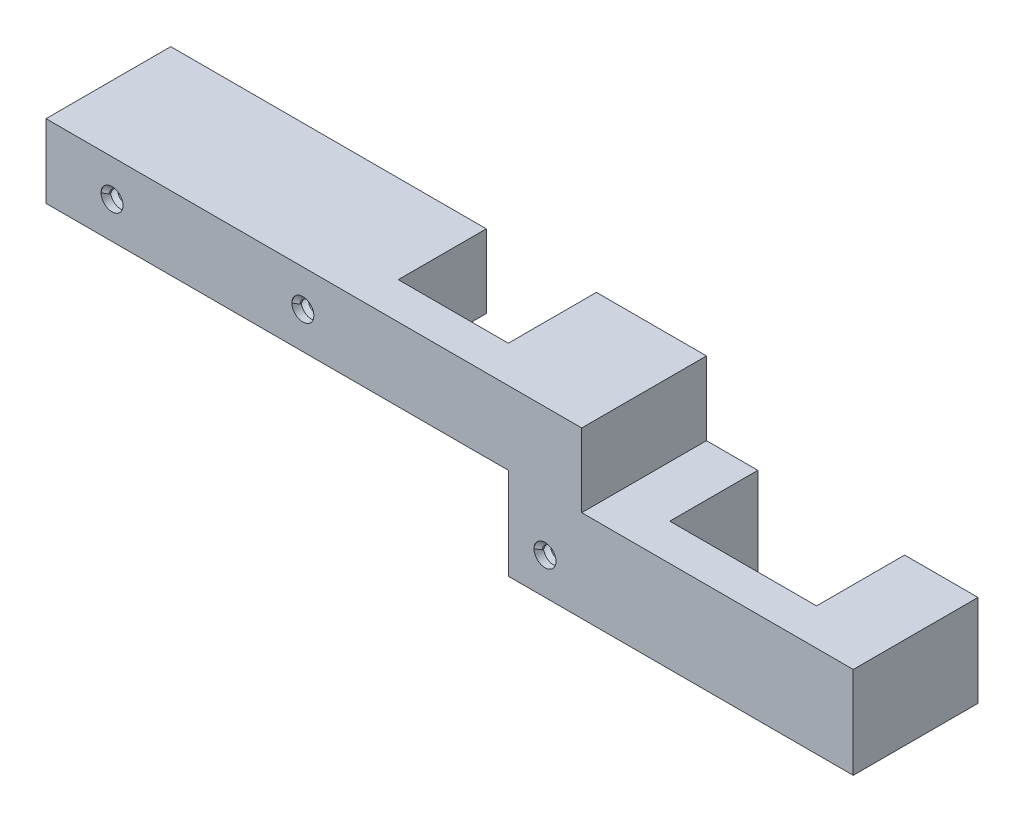
SolidWorks part; units mm, degrees
ref_plane "Alzado" through (0, 0, 0) normal (0, 0, 1) x (1, 0, 0)
ref_plane "Planta" through (0, 0, 0) normal (0, 1, 0) x (1, 0, 0)
ref_plane "Vista lateral" through (0, 0, 0) normal (1, 0, 0) x (0, 0, -1)
sketch "Croquis1" plane through (0, 0, 0) normal (0, 0, 1) x (1, 0, 0)
  line L0 (-66.626, 7.7371) -> (-3.626, 7.7371)
  line L2 (-66.626, 17.7371) -> (-66.626, 7.7371)
  line L6 (-3.626, 7.7371) -> (-3.626, -4.7629)
  line L7 (-3.626, -4.7629) -> (43.374, -4.7629)
  line L8 (43.374, 7.7371) -> (43.374, -4.7629)
  line L9 (6.374, 7.7371) -> (43.374, 7.7371)
  line L10 (6.374, 7.7371) -> (6.374, 17.7371)
  line L11 (6.374, 17.7371) -> (-66.626, 17.7371)
  circle A0 centre (-31.626, 12.7371) radius 1.5
  circle A1 centre (-57.626, 12.7371) radius 1.5
  circle A2 centre (1.374, 0.2371) radius 1.5
  dimension "D4" = 3
  dimension "D5" = 3
  dimension "D7" = 3
  dimension "D2" = 10
  dimension "D6" = 26
  dimension "D11" = 5
  dimension "D12" = 5
extrude "Saliente-Extruir1" add sketch "Croquis1" along normal blind 17
thread "Rosca1" pitch 1.25 method extrude profile "Perfil de rosca1" start angle 0, offset 0, length 15, pitch 1.25, diameter 3
ref_plane "Plano1" through (-33.126, 12.7371, 17) normal (0, -1, 0) x (-1, 0, 0)
sketch "Perfil de rosca1" plane through (-33.126, 12.7371, 17) normal (0, -1, 0) x (-1, 0, 0)
  line L0 (0, 0) -> (0, 1.25) construction
  line L11 (0, 0) -> (0, 1.0937)
  line L12 (0, 1.0937) -> (-0.6766, 0.7031)
  line L13 (-0.6766, 0.7031) -> (-0.6766, 0.3906)
  line L15 (-0.6766, 0.3906) -> (0, 0)
  line L17 (-0.6766, 0.5469) -> (0, 0.5469) construction
  point P2 (0, 0)
  dimension "Pitch" = 1.25
  dimension "Profile_Angle" = 60
  dimension "Profile_Land" = 0.3125
  dimension "Profile_Height" = 0.6766
thread "Rosca2" pitch 1.25 method extrude profile "Perfil de rosca2" start angle 0, offset 0, length 15, pitch 1.25, diameter 3
ref_plane "Plano2" through (-59.126, 12.7371, 17) normal (0, -1, 0) x (-1, 0, 0)
sketch "Perfil de rosca2" plane through (-59.126, 12.7371, 17) normal (0, -1, 0) x (-1, 0, 0)
  line L0 (0, 0) -> (0, 1.25) construction
  line L11 (0, 0) -> (0, 1.0937)
  line L12 (0, 1.0937) -> (-0.6766, 0.7031)
  line L13 (-0.6766, 0.7031) -> (-0.6766, 0.3906)
  line L15 (-0.6766, 0.3906) -> (0, 0)
  line L17 (-0.6766, 0.5469) -> (0, 0.5469) construction
  point P2 (0, 0)
  dimension "Pitch" = 1.25
  dimension "Profile_Angle" = 60
  dimension "Profile_Land" = 0.3125
  dimension "Profile_Height" = 0.6766
thread "Rosca3" pitch 1.25 method extrude profile "Perfil de rosca3" start angle 0, offset 0, length 15, pitch 1.25, diameter 3
ref_plane "Plano3" through (-0.126, 0.2371, 17) normal (0, -1, 0) x (-1, 0, 0)
sketch "Perfil de rosca3" plane through (-0.126, 0.2371, 17) normal (0, -1, 0) x (-1, 0, 0)
  line L0 (0, 0) -> (0, 1.25) construction
  line L11 (0, 0) -> (0, 1.0937)
  line L12 (0, 1.0937) -> (-0.6766, 0.7031)
  line L13 (-0.6766, 0.7031) -> (-0.6766, 0.3906)
  line L15 (-0.6766, 0.3906) -> (0, 0)
  line L17 (-0.6766, 0.5469) -> (0, 0.5469) construction
  point P2 (0, 0)
  dimension "Pitch" = 1.25
  dimension "Profile_Angle" = 60
  dimension "Profile_Land" = 0.3125
  dimension "Profile_Height" = 0.6766
sketch "Croquis9" plane through (0, -4.7629, 0) normal (0, -1, 0) x (1, 0, 0)
  line L1 (13.374, 0) -> (33.374, 0)
  line L2 (13.374, 0) -> (13.374, 12)
  line L3 (13.374, 12) -> (33.374, 12)
  line L4 (33.374, 0) -> (33.374, 12)
  line L7 (43.374, 17) -> (43.374, 0) construction
  line L12 (-3.626, 17) -> (43.374, 17) construction
  line L13 (-3.626, 17) -> (-3.626, 0) construction
  line L22 (-8.626, 0) -> (-23.626, 0)
  line L23 (-8.626, 0) -> (-8.626, 12)
  line L24 (-8.626, 12) -> (-23.626, 12)
  line L25 (-23.626, 0) -> (-23.626, 12)
  point P17 (0, 0)
  dimension "D1" = 10
  dimension "D2" = 5
  dimension "D3" = 20
  dimension "D4" = 5
  dimension "D5" = 15
extrude "Cortar-Extruir1" cut sketch "Croquis9" against normal up to vertex (22.5 mm away) contours L23 L22 L25 L24 | L2 L1 L4 L3 up to point (6.374, 17.7371, 17)
